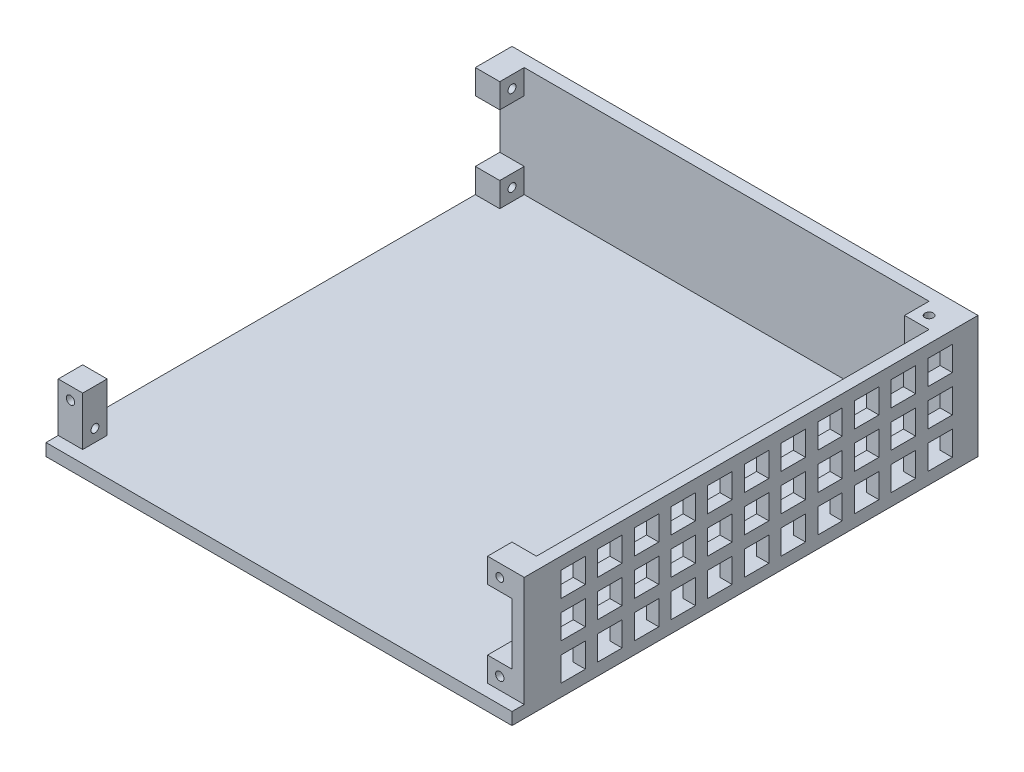
SolidWorks part; units mm, degrees
ref_plane "Front Plane" through (0, 0, 0) normal (0, 0, 1) x (1, 0, 0)
ref_plane "Top Plane" through (0, 0, 0) normal (0, 1, 0) x (1, 0, 0)
ref_plane "Right Plane" through (0, 0, 0) normal (1, 0, 0) x (0, 0, -1)
sketch "Sketch1" plane through (0, 0, 0) normal (0, 1, 0) x (1, 0, 0)
  line L1 (-95.25, 95.25) -> (95.25, 95.25)
  line L2 (-95.25, 95.25) -> (-95.25, -95.25)
  line L3 (-95.25, -95.25) -> (95.25, -95.25)
  line L4 (95.25, 95.25) -> (95.25, -95.25)
  line L5 (-95.25, 95.25) -> (95.25, -95.25) construction
  line L6 (-95.25, -95.25) -> (95.25, 95.25) construction
  point P0 (0, 0)
  dimension "D1" = 190.5
  dimension "D2" = 190.5
extrude "Boss-Extrude1" add sketch "Sketch1" along normal blind 5
sketch "Sketch9" plane through (0, 5, 0) normal (0, 1, 0) x (1, 0, 0)
  line L0 (95.25, -95.25) -> (95.25, 95.25) construction
  line L1 (-95.25, 95.25) -> (95.25, 95.25)
  line L2 (-95.25, 95.25) -> (-95.25, 90.25)
  line L3 (-95.25, 90.25) -> (95.25, 90.25)
  line L4 (95.25, 95.25) -> (95.25, 90.25)
  dimension "D1" = 5
extrude "Boss-Extrude5" add sketch "Sketch9" along normal blind 45
sketch "Sketch10" plane through (0, 5, 0) normal (0, 1, 0) x (1, 0, 0)
  line L0 (-95.25, -95.25) -> (95.25, -95.25) construction
  line L1 (95.25, 90.25) -> (90.25, 90.25)
  line L2 (95.25, 90.25) -> (95.25, -95.25)
  line L3 (95.25, -95.25) -> (90.25, -95.25)
  line L4 (90.25, 90.25) -> (90.25, -95.25)
  dimension "D1" = 5
extrude "Boss-Extrude6" add sketch "Sketch10" along normal up to surface (45 mm away) up to face at (0, 50, -92.75)
sketch "Sketch11" plane through (95.25, 0, 0) normal (1, 0, 0) x (0, 0, -1)
  line L0 (-95.25, 50) -> (95.25, 50) construction
  line L1 (-65.25, 45) -> (-75.25, 45)
  line L2 (-65.25, 45) -> (-65.25, 35)
  line L3 (-65.25, 35) -> (-75.25, 35)
  line L4 (-75.25, 45) -> (-75.25, 35)
  line L5 (-95.25, 50) -> (-95.25, 0) construction
  dimension "D1" = 5
  dimension "D2" = 20
  dimension "D3" = 10
  dimension "D4" = 10
extrude "Cut-Extrude3" cut sketch "Sketch11" against normal up to surface (5 mm away) up to face at (90.25, 27.5, 2.5)
pattern_linear "LPattern3" count 3 spacing 15 along (0, -1, 0) of "Cut-Extrude3"
pattern_linear "LPattern4" count 11 spacing 15 along (0, 0, -1) of "LPattern3"
sketch "Sketch12" plane through (-95.25, 0, 0) normal (-1, 0, 0) x (0, 0, 1)
  line L1 (-90.25, 5) -> (-80.25, 5)
  line L2 (-90.25, 5) -> (-90.25, 15)
  line L3 (-90.25, 15) -> (-80.25, 15)
  line L4 (-80.25, 5) -> (-80.25, 15)
  dimension "D1" = 10
  dimension "D2" = 10
extrude "Boss-Extrude7" add sketch "Sketch12" against normal blind 10
mirror "Mirror1" about plane through (0, 0, 0) normal (0, 0, 1) of "Boss-Extrude7"
sketch "Sketch13" plane through (0, 50, 0) normal (0, 1, 0) x (1, 0, 0)
  line L0 (90.25, 90.25) -> (90.25, -95.25) construction
  line L1 (95.25, -95.25) -> (90.25, -95.25)
  line L2 (95.25, -95.25) -> (95.25, -90.25)
  line L3 (95.25, -90.25) -> (90.25, -90.25)
  line L4 (90.25, -95.25) -> (90.25, -90.25)
  dimension "D1" = 5
extrude "Cut-Extrude4" cut sketch "Sketch13" against normal up to surface (45 mm away) up to face at (65.5463, 5, -0.3426)
sketch "Sketch14" plane through (-95.25, 0, 0) normal (-1, 0, 0) x (0, 0, 1)
  line L0 (80.25, 15) -> (90.25, 15) construction
  line L1 (80.25, 5) -> (80.25, 15) construction
  circle A0 centre (85.25, 10) radius 1.625
  point P4 (85.25, 15)
  point P7 (80.25, 10)
  dimension "D1" = 3.25
extrude "Cut-Extrude5" cut sketch "Sketch14" against normal up to surface (10 mm away) up to face at (-85.25, 10, 85.25)
mirror "Mirror2" about plane through (0, 0, 0) normal (0, 0, 1) of "Cut-Extrude5"
sketch "Sketch15" plane through (0, 0, -90.25) normal (0, 0, 1) x (1, 0, 0)
  line L1 (-95.25, 50) -> (-85.25, 50)
  line L2 (-95.25, 50) -> (-95.25, 40)
  line L3 (-95.25, 40) -> (-85.25, 40)
  line L4 (-85.25, 50) -> (-85.25, 40)
  line L5 (90.25, 50) -> (80.25, 50)
  line L6 (90.25, 50) -> (90.25, 40)
  line L7 (90.25, 40) -> (80.25, 40)
  line L8 (80.25, 50) -> (80.25, 40)
  dimension "D1" = 10
  dimension "D2" = 10
extrude "Boss-Extrude8" add sketch "Sketch15" along normal blind 10
sketch "Sketch16" plane through (-95.25, 0, 0) normal (-1, 0, 0) x (0, 0, 1)
  line L0 (-80.25, 50) -> (-80.25, 40) construction
  circle A0 centre (-85.25, 45) radius 1.625
  circle A1 centre (-85.25, 10) radius 1.625 construction
  point P8 (-80.25, 45)
  dimension "D1" = 5
extrude "Cut-Extrude6" cut sketch "Sketch16" against normal up to surface (10 mm away) up to face at (-85.25, 45, -85.25)
sketch "Sketch17" plane through (0, 50, 0) normal (0, 1, 0) x (1, 0, 0)
  line L1 (80.25, 80.25) -> (80.25, 90.25) construction
  line L2 (90.25, 80.25) -> (80.25, 80.25) construction
  circle A0 centre (85.25, 85.25) radius 1.7
  dimension "D1" = 3.4
  dimension "D2" = 5
  dimension "D3" = 5
extrude "Cut-Extrude7" cut sketch "Sketch17" against normal up to surface (10 mm away) up to face at (86.25, 40, -85.15)
sketch "Sketch18" plane through (90.25, 0, 0) normal (-1, 0, 0) x (0, 0, 1)
  line L1 (90.25, 50) -> (80.25, 50)
  line L2 (90.25, 50) -> (90.25, 40)
  line L3 (90.25, 40) -> (80.25, 40)
  line L4 (80.25, 50) -> (80.25, 40)
  dimension "D1" = 10
  dimension "D2" = 10
extrude "Boss-Extrude9" add sketch "Sketch18" along normal blind 10
sketch "Sketch19" plane through (0, 0, 90.25) normal (0, 0, 1) x (1, 0, 0)
  line L0 (80.25, 40) -> (80.25, 50) construction
  line L1 (80.25, 40) -> (90.25, 40) construction
  circle A0 centre (85.25, 45) radius 1.6
  dimension "D1" = 5
  dimension "D2" = 3.2
  dimension "D3" = 5
extrude "Cut-Extrude8" cut sketch "Sketch19" against normal up to surface (10 mm away) up to face at (85.25, 45, 80.25)
sketch "Sketch20" plane through (0, 0, 90.25) normal (0, 0, 1) x (1, 0, 0)
  line L1 (-85.25, 15) -> (-95.25, 15)
  line L2 (-85.25, 15) -> (-85.25, 25)
  line L3 (-85.25, 25) -> (-95.25, 25)
  line L4 (-95.25, 15) -> (-95.25, 25)
  dimension "D1" = 10
  dimension "D2" = 10
extrude "Boss-Extrude10" add sketch "Sketch20" against normal up to surface (10 mm away) up to face at (-90.25, 10, 80.25)
sketch "Sketch21" plane through (0, 0, 90.25) normal (0, 0, 1) x (1, 0, 0)
  line L0 (-85.25, 25) -> (-95.25, 25) construction
  line L1 (-85.25, 25) -> (-85.25, 5) construction
  circle A0 centre (-90.25, 20) radius 1.7
  dimension "D1" = 3.4
  dimension "D2" = 5
  dimension "D3" = 5
extrude "Cut-Extrude9" cut sketch "Sketch21" against normal up to surface (10 mm away) up to face at (-90.25, 15, 80.25)
sketch "Sketch22" plane through (90.25, 0, 0) normal (-1, 0, 0) x (0, 0, 1)
  line L1 (90.25, 5) -> (80.25, 5)
  line L2 (90.25, 5) -> (90.25, 15)
  line L3 (90.25, 15) -> (80.25, 15)
  line L4 (80.25, 5) -> (80.25, 15)
  dimension "D1" = 10
  dimension "D2" = 10
extrude "Boss-Extrude11" add sketch "Sketch22" along normal blind 10
sketch "Sketch23" plane through (0, 0, 90.25) normal (0, 0, 1) x (1, 0, 0)
  line L0 (80.25, 5) -> (80.25, 15) construction
  line L1 (80.25, 15) -> (90.25, 15) construction
  circle A0 centre (85.25, 10) radius 1.7
  dimension "D1" = 3.4
  dimension "D2" = 5
  dimension "D3" = 5
extrude "Cut-Extrude10" cut sketch "Sketch23" against normal up to surface (10 mm away) up to face at (85.25, 10, 80.25)
